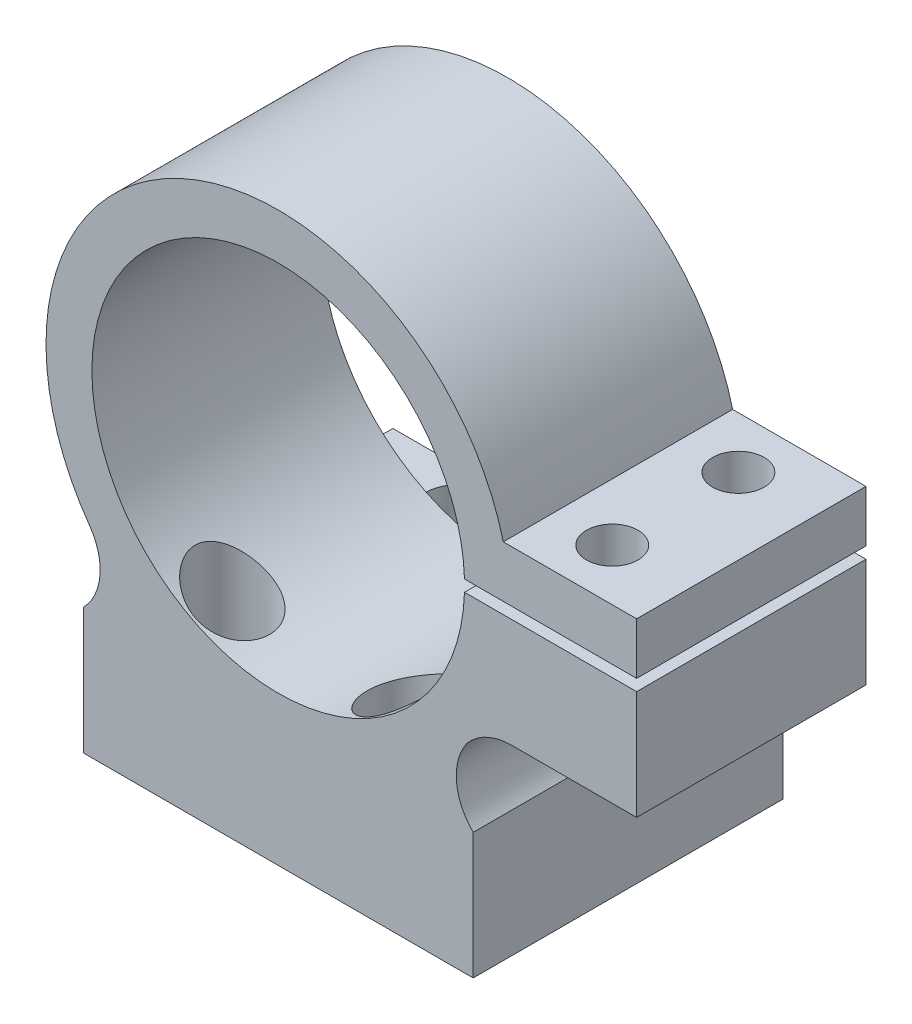
SolidWorks part; units mm, degrees
ref_plane "Front" through (0, 0, 0) normal (0, 0, 1) x (1, 0, 0)
ref_plane "Top" through (0, 0, 0) normal (0, 1, 0) x (1, 0, 0)
ref_plane "Right" through (0, 0, 0) normal (1, 0, 0) x (0, 0, -1)
sketch "Sketch1" plane through (0, 0, 0) normal (0, 1, 0) x (1, 0, 0)
  line L1 (17, -13.5) -> (-17, -13.5)
  line L2 (17, -13.5) -> (17, 13.5)
  line L3 (17, 13.5) -> (-17, 13.5)
  line L4 (-17, -13.5) -> (-17, 13.5)
  line L5 (17, -13.5) -> (-17, 13.5) construction
  line L6 (17, 13.5) -> (-17, -13.5) construction
  point P0 (0, 0)
  dimension "D1" = 27
  dimension "D2" = 34
extrude "Boss-Extrude1" add sketch "Sketch1" along normal blind 11
sketch "Sketch3" plane through (0, 11, 0) normal (0, 1, 0) x (-1, 0, 0)
  line B0 (17, -12) -> (17, 12)
  line B1 (-17, -12) -> (-17, 12)
  line B2 (11, -13.5) -> (-11, -13.5)
  line B3 (11, 13.5) -> (-11, 13.5)
  line B4 (-11, 12) -> (-17, 12)
  line B5 (-11, -12) -> (-17, -12)
  line B6 (0, 13.5) -> (0, 0) construction
  line B7 (7.5, -10) -> (-7.5, -10) construction
  line B8 (7.5, 10) -> (-7.5, 10) construction
  line B9 (-7.5, -10) -> (-7.5, 10) construction
  line B10 (7.5, -10) -> (-7.5, 10) construction
  line B11 (7.5, 10) -> (-7.5, -10) construction
sketch_block_instance "TW-04-12-1"
sketch_block "TW-04-12" parameters "D1"=22, "D2"=34, "D3"=27, "D4"=24, "D5"=20, "D6"=15
sketch "Sketch2" plane through (0, 0, 13.5) normal (0, 0, 1) x (1, 0, 0)
  line L0 (0, 29.25) -> (0, 0) construction
  line L1 (-17, 11) -> (17, 11) construction
  line L3 (17, 13) -> (-17, 13) construction
  line L4 (-17, 0) -> (17, 0) construction
  circle A0 centre (0, 29.25) radius 20.25
  circle A1 centre (0, 29.25) radius 16.25
  point P3 (0, 0)
  dimension "D1" = 4
  dimension "D2" = 40.5
  dimension "D3" = 32.5
  dimension "D4" = 2
  dimension "D5" = 29.25
  dimension "D6" = 0
extrude "Motor Clamp Band" add sketch "Sketch2" against normal blind 20
fillet "Fillet4" radius 5 1 edges at (8.775, 11, 3.5)
sketch "Sketch7" plane through (0, 0, 13.5) normal (0, 0, 1) x (1, 0, 0)
  line L0 (16.25, 29.25) -> (31.25, 29.25) construction
  line L1 (16.25, 34.25) -> (31.25, 34.25)
  line L2 (16.25, 34.25) -> (16.25, 19.25)
  line L3 (16.25, 19.25) -> (31.25, 19.25)
  line L4 (31.25, 34.25) -> (31.25, 19.25)
  line L5 (0, 29.25) -> (16.25, 29.25) construction
  circle A1 centre (0, 29.25) radius 16.25 construction
  dimension "D1" = 15
  dimension "D2" = 15
  dimension "D3" = 10
extrude "Boss-Extrude3" add sketch "Sketch7" against normal blind 20
fillet "Fillet5" radius 5 1 edges at (-8.775, 11, 3.5)
hole_wizard "CBORE for M3 SHCS1" positions "Sketch5" profile "Sketch4" counterbore size "M3" standard "Ansi Metric" end condition through all
sketch "Sketch5" plane through (0, 11, 0) normal (0, 1, 0) x (-1, 0, 0)
  point P0 (-7.5, -10)
  point P1 (7.5, -10)
  point P4 (7.5, 10)
  point P7 (-7.5, 10)
sketch "Sketch4" plane through (7.5, 11, -10) normal (1, 0, 0) x (0, 0, 1)
  line L0 (0, 0) -> (0, 11)
  line L1 (0, 11) -> (1.7, 11)
  line L3 (1.7, 11) -> (1.7, 3)
  line L4 (1.7, 3) -> (3.25, 3)
  line L5 (3.25, 3) -> (3.25, 0)
  line L7 (3.25, 0) -> (0, 0)
  line L11 (0, -6.35) -> (0, 107.95) construction
  dimension "Thru Hole Dia." = 3.4
  dimension "Thru Hole Depth" = 11
  dimension "C'Bore Dia." = 6.5
  dimension "C'Bore Depth" = 3
sketch "Sketch6" plane through (0, 11, 0) normal (0, 1, 0) x (1, 0, 0)
  circle A0 centre (7.5, -10) radius 3.25 construction
  circle A2 centre (7.5, -10) radius 3.25
  circle A3 centre (-7.5, -10) radius 3.25 construction
  circle A4 centre (-7.5, -10) radius 3.25
extrude "Extended CounterBore 1" cut sketch "Sketch6" along normal blind 15
sketch "Sketch8" plane through (0, 34.25, 0) normal (0, 1, 0) x (1, 0, 0)
  line L0 (19.623, -3.5) -> (24.623, -3.5) construction
  line L1 (19.623, 6.5) -> (19.623, -13.5) construction
  line L2 (24.623, 2) -> (24.623, -9) construction
  dimension "D1" = 11
  dimension "D2" = 5
hole_wizard "M4 Clearance Hole1" positions "Sketch10" profile "Sketch11" hole size "M4" standard "Ansi Metric" end condition up to next
sketch "Sketch10" plane through (0, 34.25, 0) normal (0, 1, 0) x (-1, 0, 0)
  point P0 (-24.623, -2)
  point P1 (-24.623, 9)
sketch "Sketch11" plane through (24.623, 34.25, -2) normal (1, 0, 0) x (0, 0, 1)
  line L0 (0, 0) -> (0, 15)
  line L1 (0, 15) -> (2.25, 15)
  line L2 (2.25, 15) -> (2.25, 0)
  line L5 (2.25, 0) -> (0, 0)
  line L11 (0, -6.35) -> (0, 107.95) construction
  dimension "Thru Hole Dia." = 4.5
  dimension "Thru Hole Depth" = 15
sketch "Sketch13" plane through (0, 19.25, 0) normal (0, -1, 0) x (1, 0, 0)
  line L1 (24.623, 12.9548) -> (21.198, 10.9774)
  line L2 (21.198, 10.9774) -> (21.198, 7.0226)
  line L3 (21.198, 7.0226) -> (24.623, 5.0452)
  line L4 (24.623, 5.0452) -> (28.048, 7.0226)
  line L5 (28.048, 7.0226) -> (28.048, 10.9774)
  line L6 (28.048, 10.9774) -> (24.623, 12.9548)
  line L7 (28.048, -0.0226) -> (24.623, 1.9548)
  line L8 (24.623, 1.9548) -> (21.198, -0.0226)
  line L9 (21.198, -0.0226) -> (21.198, -3.9774)
  line L10 (21.198, -3.9774) -> (24.623, -5.9548)
  line L11 (24.623, -5.9548) -> (28.048, -3.9774)
  line L12 (28.048, -3.9774) -> (28.048, -0.0226)
  circle A0 centre (24.623, 9) radius 3.425 construction
  circle A1 centre (24.623, -2) radius 3.425 construction
  dimension "D1" = 6.85
extrude "Cut-Extrude2" cut sketch "Sketch13" against normal blind 3
sketch "Sketch14" plane through (0, 0, 13.5) normal (0, 0, 1) x (1, 0, 0)
  line L0 (31.25, 19.25) -> (31.25, 34.25) construction
  line L1 (16.2423, 28.75) -> (31.25, 28.75)
  line L2 (16.2423, 28.75) -> (16.2423, 29.75)
  line L3 (16.2423, 29.75) -> (31.25, 29.75)
  line L4 (31.25, 28.75) -> (31.25, 29.75)
  line L5 (31.25, 29.25) -> (16.2423, 29.25) construction
  circle A0 centre (0, 29.25) radius 16.25 construction
  point P10 (0, 29.25)
  dimension "D1" = 1
extrude "Cut-Extrude3" cut sketch "Sketch14" against normal through all
fillet "Fillet3" radius 5 1 edges at (17.6086, 19.25, 3.5)
